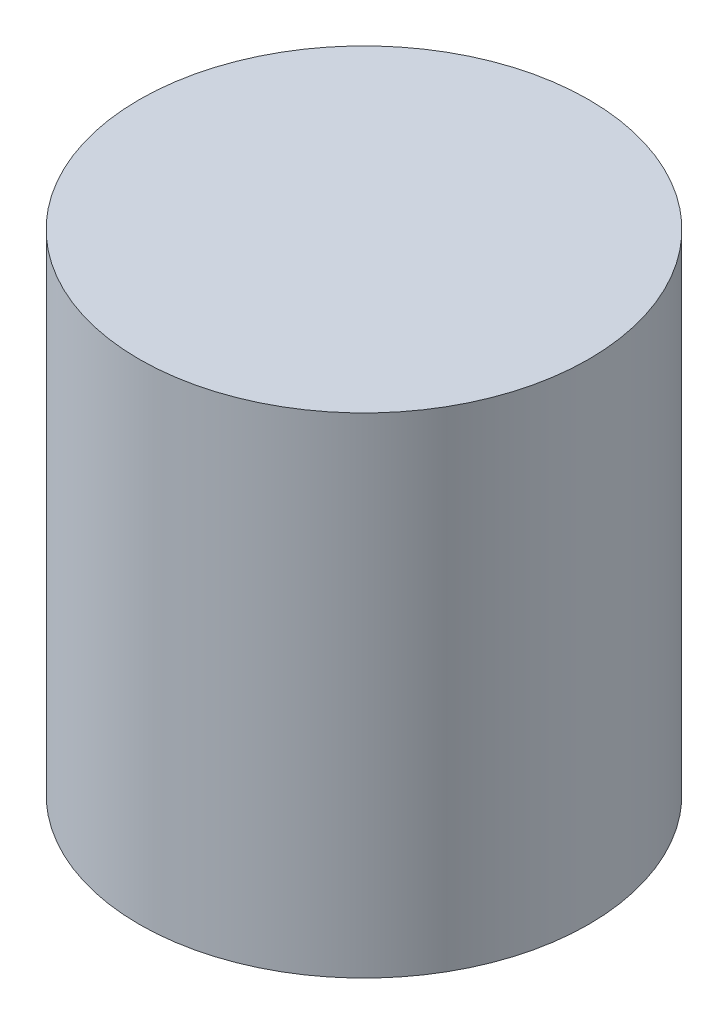
SolidWorks part; units mm, degrees
ref_plane "Front Plane" through (0, 0, 0) normal (0, 0, 1) x (1, 0, 0)
ref_plane "Top Plane" through (0, 0, 0) normal (0, 1, 0) x (1, 0, 0)
ref_plane "Right Plane" through (0, 0, 0) normal (1, 0, 0) x (0, 0, -1)
sketch "Sketch1" plane through (0, 0, 0) normal (0, 1, 0) x (1, 0, 0)
  line L0 (-0.585, 0.585) -> (-0.585, 2.05)
  line L1 (-0.585, 2.05) -> (0.585, 2.05)
  line L2 (0.585, 2.05) -> (0.585, 0.585)
  line L3 (0.585, 0.585) -> (2.05, 0.585)
  line L4 (2.05, 0.585) -> (2.05, -0.585)
  line L5 (2.05, -0.585) -> (0.585, -0.585)
  line L6 (0.585, -0.585) -> (0.585, -2.05)
  line L7 (0.585, -2.05) -> (-0.585, -2.05)
  line L8 (-0.585, -2.05) -> (-0.585, -0.585)
  line L9 (-0.585, -0.585) -> (-2.05, -0.585)
  line L10 (-2.05, -0.585) -> (-2.05, 0.585)
  line L11 (-2.05, 0.585) -> (-0.585, 0.585)
  line L12 (-2.05, 0) -> (2.05, 0) construction
  line L13 (0, -2.05) -> (0, 2.05) construction
  circle A0 centre (0, 0) radius 2.7559
  dimension "D1" = 5.5118
  dimension "D2" = 4.1
  dimension "D3" = 4.1
  dimension "D4" = 1.17
extrude "Boss-Extrude1" add sketch "Sketch1" along normal blind 3.7 contours A0 L10 L11 L0 L1 L2 L3 L4 L5 L6 L7 L8 L9 region at (-2.678, 0, 0)
extrude "Boss-Extrude2" add sketch "Sketch1<3>" along normal blind 2.3 from surface contours A0 starting at face at (0, 3.7, 0)
sketch "Sketch1<3>" plane through (0, 0, 0) normal (0, 1, 0) x (1, 0, 0) same geometry as "Sketch1"
